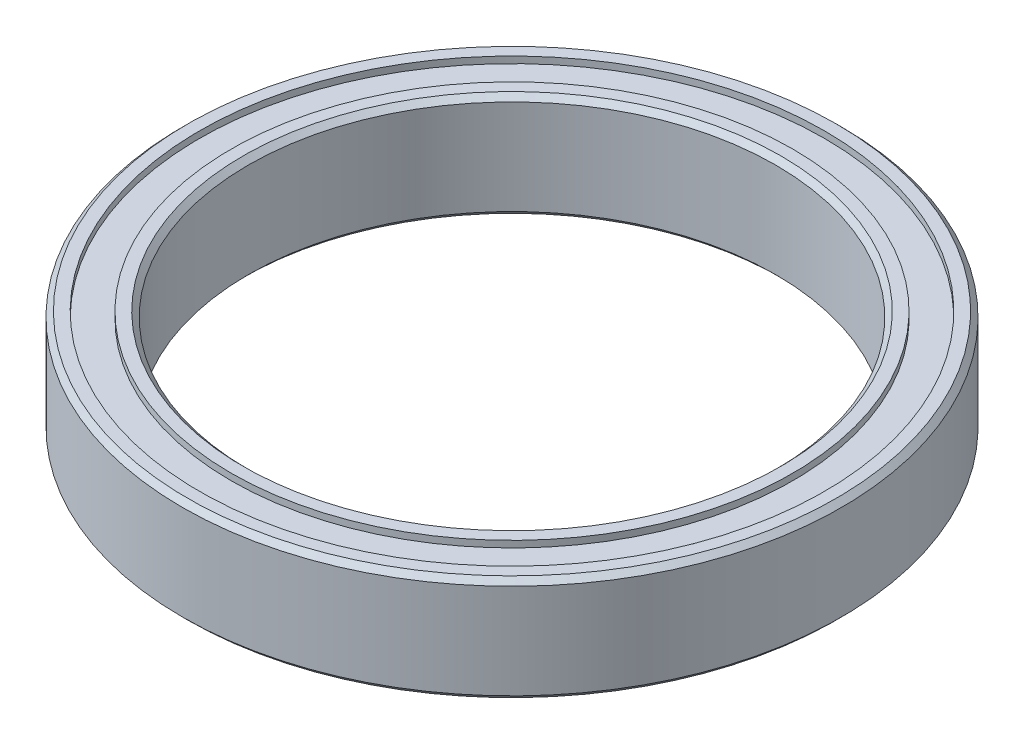
SolidWorks part; units mm, degrees
ref_plane "Ebene vorne" through (0, 0, 0) normal (0, 0, 1) x (1, 0, 0)
ref_plane "Ebene oben" through (0, 0, 0) normal (0, 1, 0) x (1, 0, 0)
ref_plane "Ebene rechts" through (0, 0, 0) normal (1, 0, 0) x (0, 0, -1)
sketch "Skizze2" plane through (0, 0, 0) normal (1, 0, 0) x (0, 0, -1)
  line L0 (0, -18.1229) -> (0, 17.8232) construction
  line L1 (-24.3396, 0) -> (24.2431, 0) construction
  line L2 (-12.5, 2) -> (-12.5, -2)
  line L3 (-12.5, -2) -> (-11.85, -2)
  line L4 (-11.85, -2) -> (-11.85, -1.75)
  line L5 (-11.85, -1.75) -> (-10.65, -1.75)
  line L6 (-10.65, -1.75) -> (-10.65, -2)
  line L7 (-10.65, -2) -> (-10, -2)
  line L8 (-10, -2) -> (-10, 2)
  line L9 (-10.65, 2) -> (-10, 2)
  line L10 (-10.65, 1.75) -> (-10.65, 2)
  line L11 (-11.85, 1.75) -> (-10.65, 1.75)
  line L12 (-11.85, 2) -> (-11.85, 1.75)
  line L13 (-12.5, 2) -> (-11.85, 2)
  point P5 (-10, 0)
  point P19 (-12.5, 0)
  dimension "D1" = 25
  dimension "D2" = 20
  dimension "D3" = 4
  dimension "D4" = 23.7
  dimension "D5" = 21.3
  dimension "D6" = 0.25
revolve "Rotation2" add sketch "Skizze2" angle 360 about L0
ref_axis "Achse1" through (0, -2.2, 0) along (0, 1, 0)
chamfer "Fase1" distance 0.2 angle 45 4 edges at (0, 2, -10) (0, -2, -10) (0, 2, -12.5) (0, -2, -12.5)
